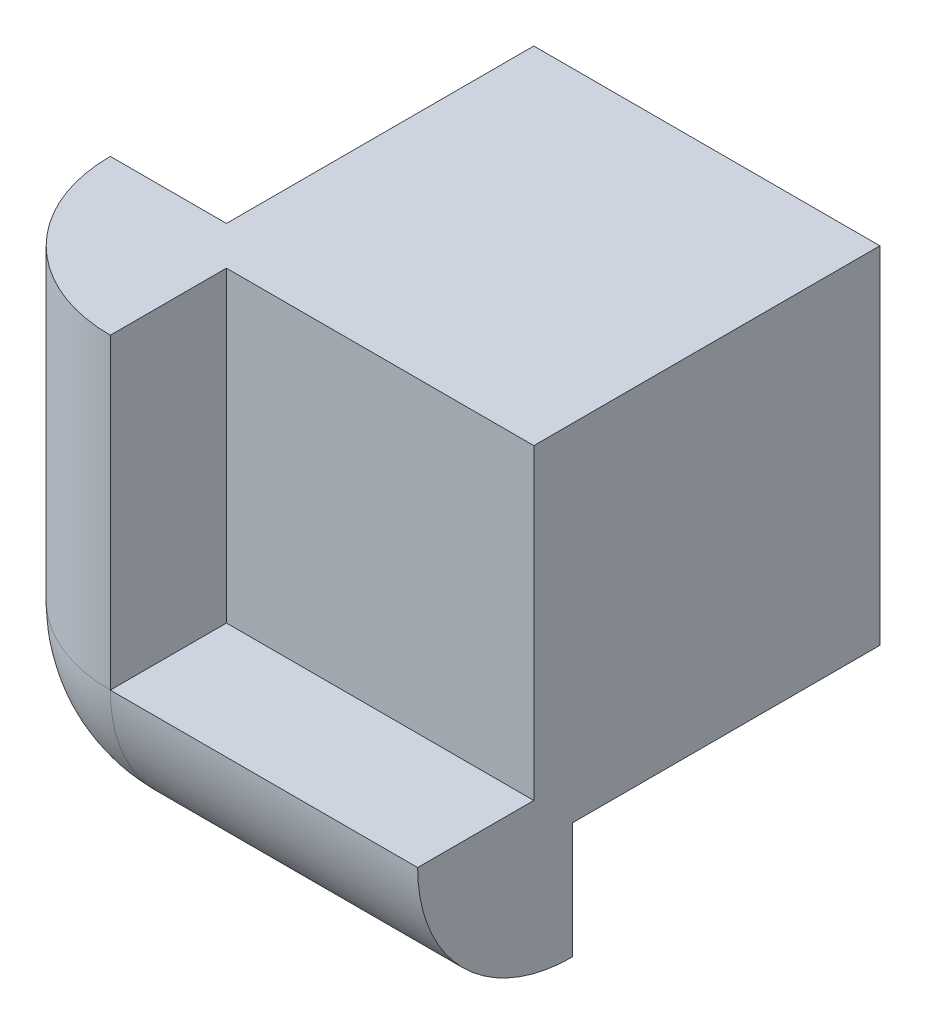
SolidWorks part; units mm, degrees
ref_plane "Front Plane" through (0, 0, 0) normal (0, 0, 1) x (1, 0, 0)
ref_plane "Top Plane" through (0, 0, 0) normal (0, 1, 0) x (1, 0, 0)
ref_plane "Right Plane" through (0, 0, 0) normal (1, 0, 0) x (0, 0, -1)
sketch "Sketch1" plane through (0, 0, 0) normal (0, 1, 0) x (1, 0, 0)
  line L0 (0, 1) -> (0, 0) construction
  line L5 (8.9375, 8.9375) -> (0, 8.9375)
  line L6 (8.9375, 8.9375) -> (8.9375, 0)
  line L7 (8.9375, 0) -> (1, 0)
  line L8 (0, 8.9375) -> (0, 1)
  line L9 (8.9375, 8.9375) -> (0, 0) construction
  line L10 (8.9375, 0) -> (0, 8.9375) construction
  line L11 (-3, -3) -> (1, -3)
  line L12 (-3, -3) -> (-3, 1)
  line L13 (-3, 1) -> (0, 1)
  line L14 (1, -3) -> (1, 0)
  line L15 (-3, -3) -> (1, 1) construction
  line L16 (-3, 1) -> (1, -3) construction
  line L17 (0, 1) -> (1, 1) construction
  line L18 (1, 0) -> (0, 0) construction
  line L19 (1, 0) -> (1, 1) construction
  point P0 (4.4687, 4.4687)
  point P7 (-1, -1)
  point P14 (-3.7465, -4)
  dimension "D1" = 1
  dimension "D2" = 4
  dimension "D3" = 8.9375
extrude "Boss-Extrude1" add sketch "Sketch1" along normal blind 8.9375
sketch "Sketch2" plane through (0, 0, 0) normal (0, 0, 1) x (1, 0, 0)
  line L0 (1, 8.9375) -> (1, 0) construction
  line L1 (-3, -3) -> (1, -3)
  line L2 (-3, -3) -> (-3, 1)
  line L3 (-3, 1) -> (1, 1)
  line L4 (1, -3) -> (1, 1)
  line L5 (-3, -3) -> (1, 1) construction
  line L6 (-3, 1) -> (1, -3) construction
  line L7 (-3, 8.9375) -> (-3, 0) construction
  point P0 (-1, -1)
extrude "Boss-Extrude4" add sketch "Sketch2" against normal up to surface (8.9375 mm away) up to face at (4.4687, 4.4687, -8.9375)
sketch "Sketch3" plane through (-3, 0, 0) normal (-1, 0, 0) x (0, 0, 1)
  line L0 (3, 8.9375) -> (3, 0) construction
  line L1 (-1, 1) -> (3, 1)
  line L2 (-1, 1) -> (-1, -3)
  line L3 (-1, -3) -> (3, -3)
  line L4 (3, 1) -> (3, -3)
extrude "Boss-Extrude5" add sketch "Sketch3" against normal up to vertex (11.9375 mm away) up to point (8.9375, 0, 0)
fillet "Fillet1" radius 4 3 edges at (-3, -3, -2.9687) (2.9687, -3, 3) (-3, 2.9687, 3)
equation "\"corner_square\"=0.35187"
equation "\"D3@Sketch1\"=\"corner_square\""
equation "\"D1@Boss-Extrude1\"=\"corner_square\""
